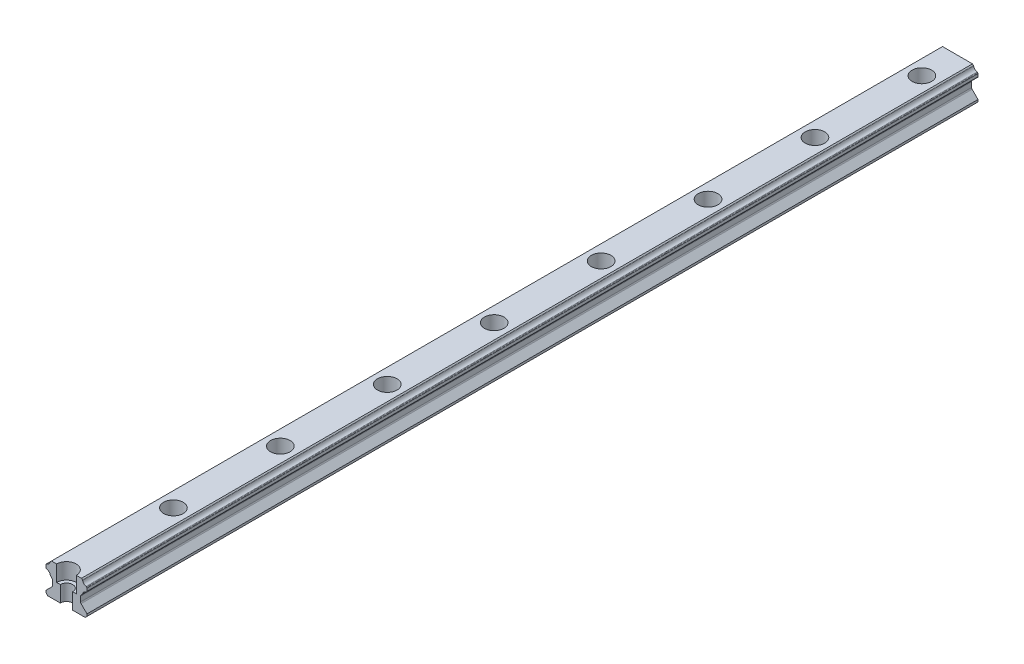
SolidWorks part; units mm, degrees
material "Plain Carbon Steel"
ref_plane "Front Plane" through (0, 0, 0) normal (0, 0, 1) x (1, 0, 0)
ref_plane "Top Plane" through (0, 0, 0) normal (0, 1, 0) x (1, 0, 0)
ref_plane "Right Plane" through (0, 0, 0) normal (1, 0, 0) x (0, 0, -1)
sketch "Sketch1" plane through (0, 0, 0) normal (0, 0, 1) x (1, 0, 0)
  line L0 (-8.1929, -12.4528) -> (-11.5, -15.7599)
  line L1 (-11.5, -17) -> (-10.5, -18)
  line L2 (0, 0) -> (0, -18) construction
  line L3 (-11.5, -15.7599) -> (-11.5, -17)
  line L4 (-10.5, -18) -> (10.5, -18)
  line L5 (11.5, -17) -> (11.5, -15.7599)
  line L6 (11.5, -15.7599) -> (8.1929, -12.4528)
  line L7 (10.5, -18) -> (11.5, -17)
  line L71 (-7.9, -11.7457) -> (-7.9, -8.9341)
  line L72 (-8.1929, -8.227) -> (-8.9352, -7.4847)
  line L73 (-11.1891, -5.2308) -> (-11.3536, -5.0663)
  line L74 (-11.5, -4.7128) -> (-11.5, -3.2984)
  line L75 (-11.3536, -2.9449) -> (-11.1751, -2.7664)
  line L76 (-8.9382, -0.5295) -> (-8.4087, 0)
  line L77 (-8.4087, 0) -> (8.4087, 0)
  line L78 (8.4087, 0) -> (8.9382, -0.5295)
  line L79 (11.1751, -2.7664) -> (11.3536, -2.9449)
  line L80 (11.5, -3.2984) -> (11.5, -4.7128)
  line L81 (11.3536, -5.0663) -> (11.1891, -5.2308)
  line L82 (8.9352, -7.4847) -> (8.1929, -8.227)
  line L83 (7.9, -8.9341) -> (7.9, -11.7457)
  arc A40 (-8.1929, -12.4528) -> (-7.9, -11.7457) centre (-8.9, -11.7457) ccw
  arc A41 (-7.9, -8.9341) -> (-8.1929, -8.227) centre (-8.9, -8.9341) ccw
  arc A42 (-9.0706, -7.2355) -> (-8.9352, -7.4847) centre (-8.5816, -7.1312) ccw
  arc A43 (-9.0706, -7.2355) -> (-10.9399, -5.3662) centre (-11.4471, -7.7427) ccw
  arc A44 (-11.1891, -5.2308) -> (-10.9399, -5.3662) centre (-10.8355, -4.8773) ccw
  arc A45 (-11.5, -4.7128) -> (-11.3536, -5.0663) centre (-11, -4.7128) ccw
  arc A46 (-11.3536, -2.9449) -> (-11.5, -3.2984) centre (-11, -3.2984) ccw
  arc A47 (-10.9283, -2.6315) -> (-11.1751, -2.7664) centre (-10.8216, -3.12) ccw
  arc A48 (-10.9283, -2.6315) -> (-9.0731, -0.7763) centre (-11.4471, -0.2575) ccw
  arc A49 (-8.9382, -0.5295) -> (-9.0731, -0.7763) centre (-8.5846, -0.883) ccw
  arc A50 (9.0731, -0.7763) -> (8.9382, -0.5295) centre (8.5846, -0.883) ccw
  arc A51 (9.0731, -0.7763) -> (10.9283, -2.6315) centre (11.4471, -0.2575) ccw
  arc A52 (11.1751, -2.7664) -> (10.9283, -2.6315) centre (10.8216, -3.12) ccw
  arc A53 (11.5, -3.2984) -> (11.3536, -2.9449) centre (11, -3.2984) ccw
  arc A54 (11.3536, -5.0663) -> (11.5, -4.7128) centre (11, -4.7128) ccw
  arc A55 (10.9399, -5.3662) -> (11.1891, -5.2308) centre (10.8355, -4.8773) ccw
  arc A56 (10.9399, -5.3662) -> (9.0706, -7.2355) centre (11.4471, -7.7427) ccw
  arc A57 (8.9352, -7.4847) -> (9.0706, -7.2355) centre (8.5816, -7.1312) ccw
  arc A58 (8.1929, -8.227) -> (7.9, -8.9341) centre (8.9, -8.9341) ccw
  arc A59 (7.9, -11.7457) -> (8.1929, -12.4528) centre (8.9, -11.7457) ccw
  point P30 (11.5, -18)
  point P40 (-11.5, -18)
  dimension "D3" = 18
  dimension "D4" = 45
  dimension "D5" = 23
extrude "Boss-Extrude1" add sketch "Sketch1" along normal blind 500
hole_wizard "CBORE for M6 Hex Socket Head Cap Screw1" positions "3DSketch1" profile "Sketch4" counterbore size "M6" standard "ISO" end condition through all
sketch3d "3DSketch1"
  line L0 (8.4087, 0, 0) -> (-8.4087, 0, 0) construction
  point P0 (0, 0, 20)
  dimension "D1" = 20
sketch "Sketch4" plane through (0, 0, 20) normal (1, 0, 0) x (0, 0, 1)
  line L0 (0, 0) -> (0, 18)
  line L1 (0, 18) -> (3.5, 18)
  line L3 (3.5, 18) -> (3.5, 9)
  line L4 (3.5, 9) -> (5.5, 9)
  line L5 (5.5, 9) -> (5.5, 0)
  line L7 (5.5, 0) -> (0, 0)
  line L11 (0, -6.35) -> (0, 107.95) construction
  dimension "Thru Hole Dia." = 7
  dimension "Thru Hole Depth" = 18
  dimension "C'Bore Dia." = 11
  dimension "C'Bore Depth" = 9
pattern_linear "LPattern1" count 9 spacing 60 along (0, 0, 1) of "CBORE for M6 Hex Socket Head Cap Screw1"
